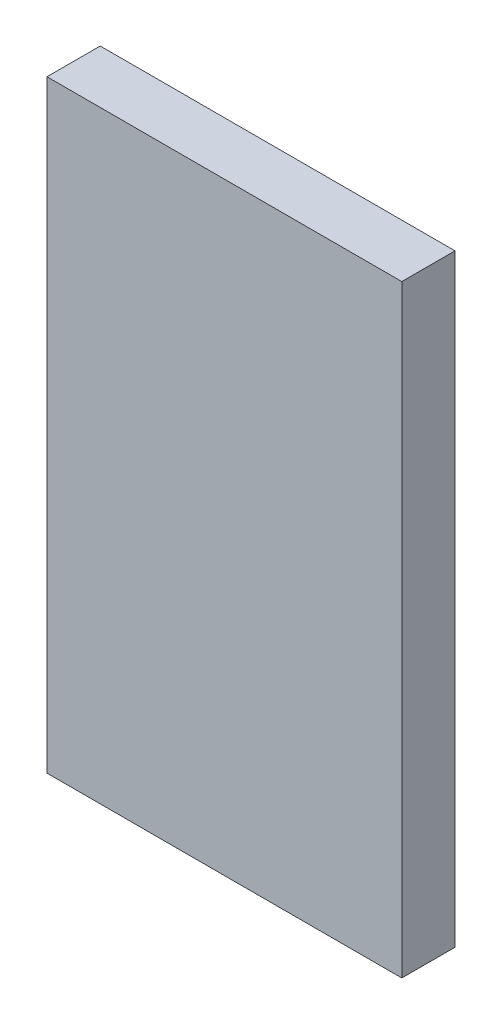
SolidWorks part; units mm, degrees
material "Silicon Rubber"
ref_plane "Front Plane" through (0, 0, 0) normal (0, 0, 1) x (1, 0, 0)
ref_plane "Top Plane" through (0, 0, 0) normal (0, 1, 0) x (1, 0, 0)
ref_plane "Right Plane" through (0, 0, 0) normal (1, 0, 0) x (0, 0, -1)
sketch "Sketch1" plane through (0, 0, 0) normal (0, 0, 1) x (1, 0, 0)
  line L0 (0, 34) -> (0, 0)
  line L1 (0, 34) -> (20, 34)
  line L2 (20, 34) -> (20, 0)
  line L3 (20, 0) -> (0, 0)
  dimension "D1" = 20
  dimension "D2" = 34
extrude "Joint Body" add sketch "Sketch1" along normal blind 3
equation "\"D1@Sketch1\"  = \"Wjoint@Parameters@RobotHandParameters.SLDPRT\""
equation "\"D2@Sketch1\"  = \"Ljointd@Parameters@RobotHandParameters.SLDPRT\" + 24"
equation "\"D1@Joint Body\" = \"Tjointp@Parameters@RobotHandParameters.SLDPRT\""
